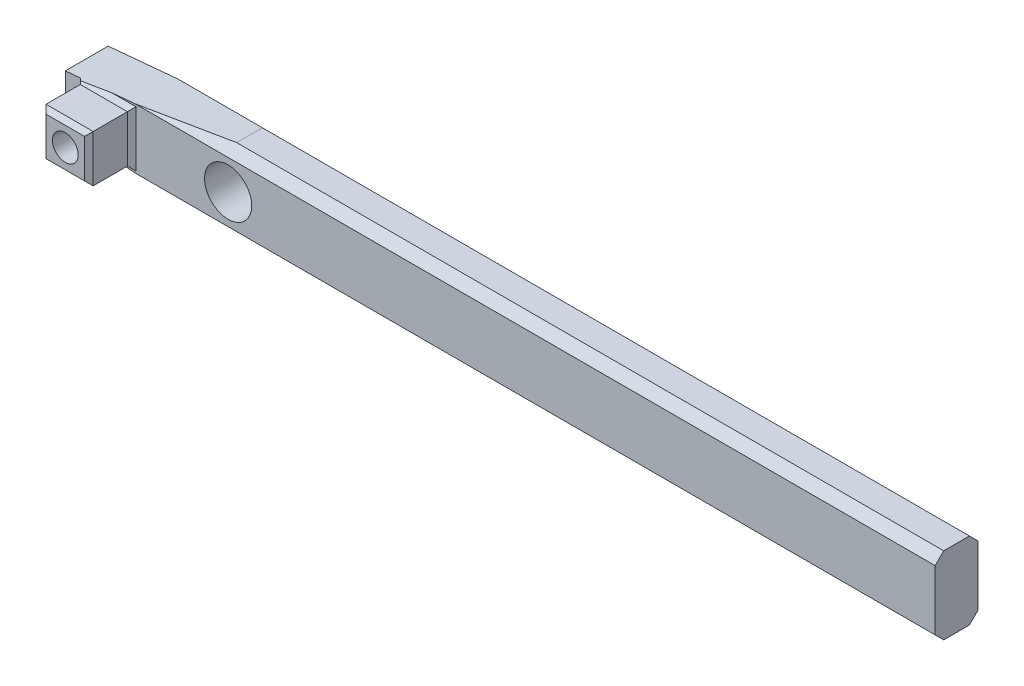
SolidWorks part; units mm, degrees
material "Nylon 101"
ref_plane "Front Plane" through (0, 0, 0) normal (0, 0, 1) x (1, 0, 0)
ref_plane "Top Plane" through (0, 0, 0) normal (0, 1, 0) x (1, 0, 0)
ref_plane "Right Plane" through (0, 0, 0) normal (1, 0, 0) x (0, 0, -1)
sketch "Sketch1" plane through (0, 0, 0) normal (0, 0, 1) x (1, 0, 0)
  line L0 (0, 0) -> (82.5, 0) construction
  line L1 (82.5, 4.5) -> (82.5, -4.5)
  line L5 (0, 0) -> (-19, 0) construction
  line L6 (0, 0) -> (0, 4.5) construction
  line L7 (0, 0) -> (0, -4.5) construction
  line L8 (0, 4.5) -> (82.5, 4.5)
  line L9 (0, -4.5) -> (82.5, -4.5)
  line L10 (-19, 2.75) -> (-19, -2.75)
  line L11 (-19, 2.75) -> (0, 4.5)
  line L12 (-19, -2.75) -> (0, -4.5)
  circle A0 centre (0, 0) radius 2.75
  point P7 (82.5, 0)
  point P13 (-19, 0)
  dimension "D1" = 5.5
  dimension "D2" = 82.5
  dimension "D3" = 9
  dimension "D4" = 19
  dimension "D5" = 5.5
extrude "Boss-Extrude1" add sketch "Sketch1" along normal blind 5
chamfer "Chamfer1" distance 1 angle 45 4 edges at (41.25, -4.5, 5) (41.25, -4.5, 0) (41.25, 4.5, 0) (41.25, 4.5, 5)
sketch "Sketch2" plane through (0, 0, 5) normal (0, 0, 1) x (1, 0, 0)
  line L0 (0, 0) -> (-19, 0) construction
  line L1 (-19, 2.75) -> (-19, -2.75) construction
  circle A0 centre (-14, 0) radius 1.5
  dimension "D2" = 3
  dimension "D1" = 5
extrude "Cut-Extrude1" cut sketch "Sketch2" against normal through all
sketch "Sketch3" plane through (0, 0, 5) normal (0, 0, 1) x (1, 0, 0)
  line L5 (-15.5, -1.5) -> (-12.5, -1.5)
  line L6 (-15.5, -1.5) -> (-15.5, 1.5)
  line L7 (-15.5, 1.5) -> (-12.5, 1.5)
  line L8 (-12.5, -1.5) -> (-12.5, 1.5)
  line L9 (-15.5, -1.5) -> (-12.5, 1.5) construction
  line L10 (-15.5, 1.5) -> (-12.5, -1.5) construction
  line L11 (-16.75, -2.75) -> (-11.25, -2.75)
  line L12 (-16.75, -2.75) -> (-16.75, 2.75)
  line L13 (-16.75, 2.75) -> (-11.25, 2.75)
  line L14 (-11.25, -2.75) -> (-11.25, 2.75)
  line L15 (-16.75, -2.75) -> (-11.25, 2.75) construction
  line L16 (-16.75, 2.75) -> (-11.25, -2.75) construction
  circle A0 centre (-14, 0) radius 1.5
  point P0 (-14, 0)
  point P6 (-14, 0)
  point P8 (-14, 0)
  circle M14 centre (-14, 0) radius 1.5
  dimension "D1" = 3
  dimension "D2" = 1.25
  dimension "D3" = 1.25
extrude "Boss-Extrude2" add sketch "Sketch3" along normal blind 5 contours L11 L14 L13 L12 L8 L5 L6 L7 | L7 L6 M14 | L6 L5 M14 | L5 L8 M14 | L8 L7 M14 region at (-15.1649, -1.1649, 5) region at (-12.8351, -1.1649, 5) region at (-15.1649, 1.1649, 5) region at (-12.8351, 1.1649, 5) region at (-16.6722, 0, 5)
chamfer "Chamfer3" distance 0.5 angle 45 8 edges at (-14, 2.75, 5) (-11.25, 0, 5) (-14, -2.75, 5) (-16.75, 0, 5) (-14, -2.75, 10) (-16.75, 0, 10) (-11.25, 0, 10) (-14, 2.75, 10)
